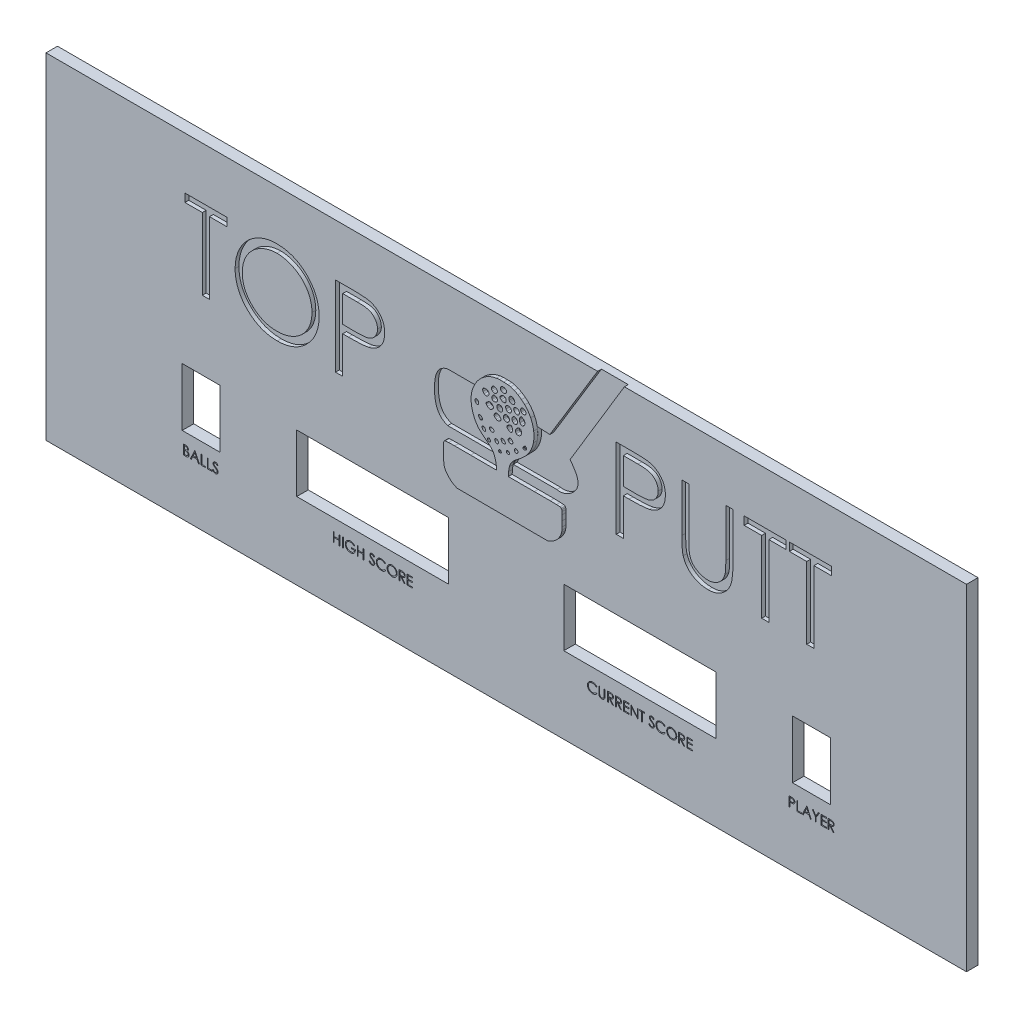
SolidWorks part; units mm, degrees
ref_plane "Front Plane" through (0, 0, 0) normal (0, 0, 1) x (1, 0, 0)
ref_plane "Top Plane" through (0, 0, 0) normal (0, 1, 0) x (1, 0, 0)
ref_plane "Right Plane" through (0, 0, 0) normal (1, 0, 0) x (0, 0, -1)
sketch "Sketch1" plane through (0, 0, 0) normal (0, 0, 1) x (1, 0, 0)
  line L1 (-152.4, 55.5625) -> (152.4, 55.5625)
  line L2 (-152.4, 55.5625) -> (-152.4, -55.5625)
  line L3 (-152.4, -55.5625) -> (152.4, -55.5625)
  line L4 (152.4, 55.5625) -> (152.4, -55.5625)
  line L5 (-152.4, 55.5625) -> (152.4, -55.5625) construction
  line L6 (-152.4, -55.5625) -> (152.4, 55.5625) construction
  point P0 (0, 0)
  dimension "D1" = 111.125
  dimension "D2" = 304.8
extrude "Boss-Extrude1" add sketch "Sketch1" along normal blind 3.81
sketch "Sketch3" plane through (0, 0, 3.81) normal (0, 0, 1) x (1, 0, 0)
  line L0 (-152.4, -30.1625) -> (152.4, -30.1625) construction
  line L1 (-152.4, 55.5625) -> (-152.4, -55.5625) construction
  line L2 (152.4, -55.5625) -> (152.4, 55.5625) construction
  line L3 (-152.4, -55.5625) -> (152.4, -55.5625) construction
  line L4 (0, 0) -> (0, -55.5625) construction
  line L5 (-94.775, -10.9805) -> (-107.3, -10.9805)
  line L6 (19.05, -30.1625) -> (69.375, -30.1625)
  line L7 (19.05, -30.1625) -> (19.05, -11.0725)
  line L8 (19.05, -11.0725) -> (69.375, -11.0725)
  line L9 (69.375, -30.1625) -> (69.375, -11.0725)
  line L10 (94.775, -30.1625) -> (107.3, -30.1625)
  line L11 (94.775, -30.1625) -> (94.775, -10.9805)
  line L12 (94.775, -10.9805) -> (107.3, -10.9805)
  line L13 (107.3, -30.1625) -> (107.3, -10.9805)
  line L14 (-107.3, -30.1625) -> (-107.3, -10.9805)
  line L15 (-94.775, -30.1625) -> (-107.3, -30.1625)
  line L16 (-94.775, -30.1625) -> (-94.775, -10.9805)
  line L17 (-19.05, -11.0725) -> (-69.375, -11.0725)
  line L18 (-69.375, -30.1625) -> (-69.375, -11.0725)
  line L19 (-19.05, -30.1625) -> (-69.375, -30.1625)
  line L20 (-19.05, -30.1625) -> (-19.05, -11.0725)
  dimension "D1" = 25.4
  dimension "D2" = 50.325
  dimension "D3" = 19.09
  dimension "D4" = 19.05
  dimension "D5" = 12.525
  dimension "D6" = 19.182
  dimension "D7" = 25.4
extrude "Cut-Extrude1" cut sketch "Sketch3" against normal blind 3.81
sketch "Sketch6" plane through (0, 0, 3.81) normal (0, 0, 1) x (1, 0, 0)
  line L0 (-107.3, -36.9875) -> (-94.775, -36.9875) construction
  line L1 (-57.6519, -37.2782) -> (-30.0792, -37.2782) construction
  line L2 (19.2892, -37.6268) -> (69.1358, -37.6268) construction
  line L3 (87.631, -37.6268) -> (114.444, -37.6268) construction
  line L4 (101.0375, -10.9805) -> (101.0375, -40.7176) construction
  line L5 (107.3, -10.9805) -> (94.775, -10.9805) construction
  line L6 (44.2125, -11.0725) -> (44.2125, -39.6653) construction
  line L7 (69.375, -11.0725) -> (19.05, -11.0725) construction
  text T0 "BALLS"
  text T1 "HIGH SCORE"
  text T2 "CURRENT SCORE"
  text T3 "PLAYER"
  point P10 (101.0375, -37.6268)
  point P19 (44.2125, -37.6268)
extrude "Cut-Extrude2" cut sketch "Sketch6" against normal blind 1.27
sketch "Sketch7" plane through (0, 0, 3.81) normal (0, 0, 1) x (1, 0, 0)
  line L20 (-1.9988, 12.5761) -> (-1.9988, 11.751)
  line L21 (-1.9988, 11.751) -> (-10.5132, 11.7768)
  line L22 (-15.9567, 0.4985) -> (-15.0481, 0.051)
  line L23 (-15.0481, 0.051) -> (0, 0)
  line L24 (0, 0) -> (15.0481, -0.051)
  line L25 (15.0481, -0.051) -> (16.2301, 0.5309)
  line L26 (10.5426, 11.862) -> (1.9524, 11.862)
  line L27 (1.9524, 11.862) -> (2.0672, 13.3498)
  line L31 (-3.3323, 25.2405) -> (-3.3323, 25.9331)
  line L32 (-5.0679, 26.8913) -> (-5.5861, 26.3948)
  line L33 (-5.5861, 26.3948) -> (-6.118, 27.1985)
  line L34 (-6.118, 27.1985) -> (-6.6498, 28.0022)
  line L35 (-6.6498, 28.0022) -> (-6.2293, 28.7329)
  line L36 (-3.7773, 36.3119) -> (-3.3529, 35.9132)
  line L37 (-3.3529, 35.9132) -> (-2.7235, 36.2908)
  arc A72 (-1.9988, 38.1147) -> (-4.7065, 37.2137) centre (-0.4765, 29.0205) ccw
  arc A73 (-4.7065, 37.2137) -> (-7.0856, 35.5114) centre (-0.0459, 28.1866) ccw
  arc A74 (-7.0856, 35.5114) -> (-8.9327, 33.1539) centre (0.3175, 27.8084) ccw
  arc A75 (-8.9327, 33.1539) -> (-10.0868, 30.3416) centre (0.8748, 27.4864) ccw
  arc A76 (-10.0868, 30.3416) -> (-10.3784, 27.9834) centre (-1.3361, 28.0623) ccw
  arc A77 (-10.3784, 27.9834) -> (-10.0835, 25.4534) centre (1.5107, 28.0871) ccw
  arc A78 (-10.0835, 25.4534) -> (-9.2506, 23.019) centre (1.7412, 28.1395) ccw
  arc A79 (-9.2506, 23.019) -> (-7.9518, 20.9428) centre (-0.2064, 27.2322) ccw
  arc A80 (-7.9518, 20.9428) -> (-7.5771, 20.537) centre (-4.5771, 23.6831) ccw
  arc A81 (-7.5771, 20.537) -> (-6.9573, 19.9681) centre (7.6292, 36.4839) ccw
  arc A82 (-6.9573, 19.9681) -> (-6.2356, 19.3549) centre (9.4942, 38.5956) ccw
  arc A83 (-6.2356, 19.3549) -> (-5.5071, 18.7837) centre (8.1333, 36.931) ccw
  arc A84 (-4.7279, 18.1675) -> (-5.5071, 18.7837) centre (-17.6705, 2.6013) ccw
  arc A85 (-4.0525, 17.5677) -> (-4.7279, 18.1675) centre (-13.5897, 7.5094) ccw
  arc A86 (-3.5128, 17.0173) -> (-4.0525, 17.5677) centre (-11.345, 9.8767) ccw
  arc A87 (-3.1609, 16.559) -> (-3.5128, 17.0173) centre (-6.0464, 14.7074) ccw
  arc A88 (-2.7104, 15.7011) -> (-3.1609, 16.559) centre (-7.8549, 13.5469) ccw
  arc A89 (-2.336, 14.6433) -> (-2.7104, 15.7011) centre (-11.9016, 11.8524) ccw
  arc A90 (-2.0823, 13.5482) -> (-2.336, 14.6433) centre (-11.9292, 11.8444) ccw
  arc A91 (-1.9988, 12.5761) -> (-2.0823, 13.5482) centre (-7.7002, 12.5761) ccw
  arc A92 (-10.5132, 11.7768) -> (-15.8316, 11.7851) centre (-15.9987, -1799.6541) ccw
  arc A93 (-15.8316, 11.7851) -> (-17.8341, 11.748) centre (-15.8365, -42.1127) ccw
  arc A94 (-17.8341, 11.748) -> (-18.9161, 11.666) centre (-17.3128, -2.308) ccw
  arc A95 (-18.9161, 11.666) -> (-19.2883, 11.4513) centre (-18.8545, 11.1292) ccw
  arc A96 (-19.2883, 11.4513) -> (-19.4186, 11.1338) centre (-18.73, 11.0367) ccw
  arc A97 (-19.4186, 11.1338) -> (-19.482, 10.4815) centre (-11.9086, 10.0751) ccw
  arc A98 (-19.482, 10.4815) -> (-19.5065, 9.4669) centre (-2.2361, 9.556) ccw
  arc A99 (-19.5065, 9.4669) -> (-19.4861, 7.7663) centre (104.1686, 10.1049) ccw
  arc A100 (-19.4861, 7.7663) -> (-19.4359, 5.7788) centre (136.9357, 10.7248) ccw
  arc A101 (-19.4359, 5.7788) -> (-19.3621, 4.8115) centre (-8.5243, 6.1239) ccw
  arc A102 (-19.3621, 4.8115) -> (-19.2237, 4.1547) centre (-15.5362, 5.2748) ccw
  arc A103 (-19.2237, 4.1547) -> (-18.9714, 3.5165) centre (-15.1935, 5.3789) ccw
  arc A104 (-18.9714, 3.5165) -> (-18.4339, 2.6452) centre (-14.1224, 5.9069) ccw
  arc A105 (-18.4339, 2.6452) -> (-17.6844, 1.7842) centre (-11.7934, 7.6688) ccw
  arc A106 (-17.6844, 1.7842) -> (-16.8249, 1.0345) centre (-11.8031, 7.659) ccw
  arc A107 (-16.8249, 1.0345) -> (-15.9567, 0.4985) centre (-13.594, 5.2965) ccw
  arc A108 (16.2301, 0.5309) -> (17.24, 1.1494) centre (13.3846, 6.3108) ccw
  arc A109 (17.24, 1.1494) -> (18.1193, 1.9421) centre (13.3896, 6.3041) ccw
  arc A110 (18.1193, 1.9421) -> (18.8359, 2.8798) centre (13.4202, 6.2759) ccw
  arc A111 (18.8359, 2.8798) -> (19.3634, 3.9283) centre (13.5385, 6.2018) ccw
  arc A112 (19.3634, 3.9283) -> (19.5889, 4.6371) centre (13.9478, 6.042) ccw
  arc A113 (19.5889, 4.6371) -> (19.714, 5.3482) centre (14.5796, 5.8846) ccw
  arc A114 (19.714, 5.3482) -> (19.7754, 6.3271) centre (7.9521, 6.577) ccw
  arc A115 (19.7754, 6.3271) -> (19.7983, 8.0917) centre (-88.8167, 8.6229) ccw
  arc A116 (19.7983, 8.0917) -> (19.7964, 9.866) centre (-128.5584, 8.8173) ccw
  arc A117 (19.7964, 9.866) -> (19.7533, 10.7144) centre (10.086, 9.7974) ccw
  arc A118 (19.7533, 10.7144) -> (19.6575, 11.21) centre (17.141, 10.4666) ccw
  arc A119 (19.6575, 11.21) -> (19.4731, 11.5207) centre (18.9527, 11.0018) ccw
  arc A120 (19.4731, 11.5207) -> (19.0432, 11.7268) centre (18.9668, 11.0158) ccw
  arc A121 (19.0432, 11.7268) -> (17.8903, 11.8106) centre (17.249, -4.9686) ccw
  arc A122 (17.8903, 11.8106) -> (15.8008, 11.8538) centre (15.6146, -47.7291) ccw
  arc A123 (15.8008, 11.8538) -> (10.5426, 11.862) centre (10.541, -1671.3002) ccw
  arc A124 (2.3284, 14.9123) -> (2.0672, 13.3498) centre (10.9883, 12.6616) ccw
  arc A125 (2.8492, 16.1436) -> (2.3284, 14.9123) centre (6.7809, 13.7551) ccw
  arc A126 (3.7446, 17.2566) -> (2.8492, 16.1436) centre (7.5014, 13.3174) ccw
  arc A127 (5.1762, 18.4675) -> (3.7446, 17.2566) centre (14.6019, 5.872) ccw
  arc A128 (5.1762, 18.4675) -> (6.4984, 19.5223) centre (-11.2086, 40.3625) ccw
  arc A129 (6.4984, 19.5223) -> (7.5394, 20.5023) centre (-2.5921, 30.2213) ccw
  arc A130 (7.5394, 20.5023) -> (8.3754, 21.4813) centre (-0.4957, 28.2102) ccw
  arc A131 (8.3754, 21.4813) -> (9.0734, 22.53) centre (0.2418, 27.6509) ccw
  arc A132 (9.0734, 22.53) -> (10.2566, 25.6998) centre (0.3306, 27.5994) ccw
  arc A133 (10.2566, 25.6998) -> (10.3539, 29.1346) centre (-0.285, 27.7172) ccw
  arc A134 (10.3539, 29.1346) -> (9.3609, 32.423) centre (-0.2778, 27.7181) ccw
  arc A135 (9.3609, 32.423) -> (7.3894, 35.1693) centre (0.3027, 28.0015) ccw
  arc A136 (7.3894, 35.1693) -> (6.3087, 36.1178) centre (-1.1236, 26.5589) ccw
  arc A137 (6.3087, 36.1178) -> (5.1303, 36.9244) centre (-0.9212, 26.8192) ccw
  arc A138 (5.1303, 36.9244) -> (3.9073, 37.5561) centre (-0.5041, 27.5156) ccw
  arc A139 (3.9073, 37.5561) -> (2.6935, 37.9815) centre (0.5388, 29.8894) ccw
  arc A140 (2.6935, 37.9815) -> (1.8123, 38.1326) centre (1.4189, 33.1946) ccw
  arc A141 (1.8123, 38.1326) -> (0.4204, 38.2078) centre (-0.3534, 10.9491) ccw
  arc A142 (0.4204, 38.2078) -> (-0.9951, 38.2105) centre (-0.3392, 11.4509) ccw
  arc A143 (-0.9951, 38.2105) -> (-1.9988, 38.1147) centre (-0.8202, 31.0736) ccw
  arc A144 (1.9506, 37.1033) -> (2.1398, 36.9355) centre (2.6538, 37.7054) ccw
  arc A145 (2.1398, 36.9355) -> (2.3755, 36.8163) centre (2.7492, 37.8482) ccw
  arc A146 (2.3755, 36.8163) -> (2.6619, 36.7456) centre (2.8528, 38.1344) ccw
  arc A147 (2.6619, 36.7456) -> (3.0026, 36.7223) centre (3.0026, 39.2238) ccw
  arc A148 (3.3292, 36.7021) -> (3.0026, 36.7223) centre (3.0026, 34.0711) ccw
  arc A149 (3.7121, 36.64) -> (3.3292, 36.7021) centre (2.6877, 31.5337) ccw
  arc A150 (4.0895, 36.5496) -> (3.7121, 36.64) centre (2.6875, 31.5325) ccw
  arc A151 (4.3988, 36.4422) -> (4.0895, 36.5496) centre (3.3743, 33.9902) ccw
  arc A152 (4.784, 36.2666) -> (4.3988, 36.4422) centre (1.8359, 30.3083) ccw
  arc A153 (4.9255, 36.1411) -> (4.784, 36.2666) centre (4.6248, 35.9448) ccw
  arc A154 (4.9476, 35.9915) -> (4.9255, 36.1411) centre (4.7741, 36.0423) ccw
  arc A155 (4.8495, 35.7517) -> (4.9476, 35.9915) centre (3.7411, 36.3449) ccw
  arc A156 (4.8495, 35.7517) -> (4.7549, 35.5183) centre (5.8958, 35.1917) ccw
  arc A157 (4.7549, 35.5183) -> (4.7439, 35.3239) centre (5.1795, 35.3968) ccw
  arc A158 (4.7439, 35.3239) -> (4.8182, 35.1186) centre (5.3397, 35.4236) ccw
  arc A159 (4.8182, 35.1186) -> (5.0017, 34.8411) centre (7.4222, 36.6413) ccw
  arc A160 (5.0017, 34.8411) -> (5.3678, 34.4786) centre (6.3777, 35.8645) ccw
  arc A161 (5.3678, 34.4786) -> (5.7824, 34.2984) centre (5.9784, 35.3166) ccw
  arc A162 (5.7824, 34.2984) -> (6.2007, 34.3213) centre (5.9458, 35.1468) ccw
  arc A163 (6.2007, 34.3213) -> (6.58, 34.5372) centre (5.903, 35.2853) ccw
  arc A164 (6.8097, 34.6751) -> (6.58, 34.5372) centre (7.0441, 34.0244) ccw
  arc A165 (6.9937, 34.6464) -> (6.8097, 34.6751) centre (6.8754, 34.4926) ccw
  arc A166 (7.2098, 34.4171) -> (6.9937, 34.6464) centre (6.3901, 33.8609) ccw
  arc A167 (7.7005, 33.6763) -> (7.2098, 34.4171) centre (-25.7222, 12.0742) ccw
  arc A168 (8.3128, 32.6868) -> (7.7005, 33.6763) centre (-17.2353, 17.5595) ccw
  arc A169 (8.5575, 32.1345) -> (8.3128, 32.6868) centre (6.0986, 31.3757) ccw
  arc A170 (8.5748, 31.7479) -> (8.5575, 32.1345) centre (7.8233, 31.9079) ccw
  arc A171 (8.4006, 31.4073) -> (8.5748, 31.7479) centre (7.8548, 31.9012) ccw
  arc A172 (8.4006, 31.4073) -> (8.1246, 30.848) centre (9.2455, 30.6427) ccw
  arc A173 (8.1246, 30.848) -> (8.1399, 30.1518) centre (9.8222, 30.537) ccw
  arc A174 (8.1399, 30.1518) -> (8.4431, 29.4431) centre (10.2485, 30.6346) ccw
  arc A175 (8.4431, 29.4431) -> (8.9852, 28.854) centre (10.5341, 30.8231) ccw
  arc A176 (9.2789, 28.5397) -> (8.9852, 28.854) centre (8.1107, 27.7422) ccw
  arc A177 (9.4149, 28.1908) -> (9.2789, 28.5397) centre (8.5931, 28.0716) ccw
  arc A178 (9.3647, 27.8926) -> (9.4149, 28.1908) centre (8.9255, 28.1198) ccw
  arc A179 (9.1523, 27.7025) -> (9.3647, 27.8926) centre (9.0087, 28.0768) ccw
  arc A180 (9.0102, 27.6969) -> (9.1523, 27.7025) centre (9.073, 27.9091) ccw
  arc A181 (8.8404, 27.7767) -> (9.0102, 27.6969) centre (9.1867, 28.2932) ccw
  arc A182 (8.6565, 27.9332) -> (8.8404, 27.7767) centre (9.4295, 28.6552) ccw
  arc A183 (8.4727, 28.1582) -> (8.6565, 27.9332) centre (10.2596, 29.4306) ccw
  arc A184 (8.4727, 28.1582) -> (8.1185, 28.5075) centre (7.2994, 27.3227) ccw
  arc A185 (8.1185, 28.5075) -> (7.7735, 28.5635) centre (7.8871, 28.1729) ccw
  arc A186 (7.7735, 28.5635) -> (7.4459, 28.3259) centre (7.9408, 27.9883) ccw
  arc A187 (7.4459, 28.3259) -> (7.1468, 27.7726) centre (9.9735, 26.6017) ccw
  arc A188 (7.1468, 27.7726) -> (7.0351, 27.4291) centre (9.2757, 26.8908) ccw
  arc A189 (7.0351, 27.4291) -> (7.0097, 27.1396) centre (7.9925, 27.199) ccw
  arc A190 (7.0097, 27.1396) -> (7.0684, 26.8133) centre (8.4186, 27.2248) ccw
  arc A191 (7.0684, 26.8133) -> (7.234, 26.3303) centre (14.1531, 28.9727) ccw
  arc A192 (7.4215, 25.6708) -> (7.234, 26.3303) centre (3.5848, 24.9367) ccw
  arc A193 (7.3678, 25.2424) -> (7.4215, 25.6708) centre (6.7346, 25.5394) ccw
  arc A194 (7.0889, 24.995) -> (7.3678, 25.2424) centre (6.9411, 25.4425) ccw
  arc A195 (6.5685, 24.9113) -> (7.0889, 24.995) centre (6.5685, 26.5706) ccw
  arc A196 (6.5685, 24.9113) -> (6.2779, 24.8678) centre (6.5685, 23.9183) ccw
  arc A197 (6.2779, 24.8678) -> (6.0439, 24.7415) centre (6.4757, 24.2214) ccw
  arc A198 (6.0439, 24.7415) -> (5.8175, 24.4947) centre (6.8354, 23.7882) ccw
  arc A199 (5.8175, 24.4947) -> (5.536, 24.054) centre (11.4216, 20.6049) ccw
  arc A200 (5.3305, 23.7256) -> (5.536, 24.054) centre (-0.2045, 27.4182) ccw
  arc A201 (5.1284, 23.4486) -> (5.3305, 23.7256) centre (1.9261, 25.9968) ccw
  arc A202 (4.949, 23.2386) -> (5.1284, 23.4486) centre (2.0335, 25.9113) ccw
  arc A203 (4.8539, 23.1968) -> (4.949, 23.2386) centre (4.8539, 23.3258) ccw
  arc A204 (4.7581, 23.2351) -> (4.8539, 23.1968) centre (4.8539, 23.3357) ccw
  arc A206 (4.3819, 23.6581) -> (4.5815, 23.4164) centre (7.2527, 25.8264) ccw
  arc A207 (4.1793, 23.9445) -> (4.3819, 23.6581) centre (8.8785, 27.0543) ccw
  arc A208 (4.1793, 23.9445) -> (3.9693, 24.2386) centre (-0.0706, 21.132) ccw
  arc A209 (3.9693, 24.2386) -> (3.7474, 24.5042) centre (0.574, 21.6278) ccw
  arc A210 (3.7474, 24.5042) -> (3.5429, 24.7126) centre (1.0186, 22.0308) ccw
  arc A211 (3.5429, 24.7126) -> (3.404, 24.7998) centre (3.2519, 24.4034) ccw
  arc A212 (3.404, 24.7998) -> (3.1041, 24.7728) centre (3.2816, 24.4809) ccw
  arc A213 (3.1041, 24.7728) -> (2.6747, 24.4492) centre (4.5104, 22.4598) ccw
  arc A214 (2.6747, 24.4492) -> (2.3057, 24.0329) centre (4.5591, 22.407) ccw
  arc A215 (2.3057, 24.0329) -> (2.1922, 23.6817) centre (2.7924, 23.6817) ccw
  arc A216 (2.1731, 23.5693) -> (2.1922, 23.6817) centre (1.8522, 23.6817) ccw
  arc A217 (2.118, 23.4738) -> (2.1731, 23.5693) centre (1.8918, 23.6678) ccw
  arc A218 (2.036, 23.4099) -> (2.118, 23.4738) centre (1.9197, 23.6439) ccw
  arc A219 (1.9396, 23.3873) -> (2.036, 23.4099) centre (1.9396, 23.6037) ccw
  arc A220 (1.6068, 23.5088) -> (1.9396, 23.3873) centre (1.9396, 23.9039) ccw
  arc A221 (1.2363, 23.899) -> (1.6068, 23.5088) centre (3.1678, 25.3622) ccw
  arc A222 (0.9035, 24.4434) -> (1.2363, 23.899) centre (3.7917, 25.8348) ccw
  arc A223 (0.6784, 25.0522) -> (0.9035, 24.4434) centre (3.9938, 25.9321) ccw
  arc A224 (0.6784, 25.0522) -> (0.5525, 25.444) centre (-3.1784, 24.0287) ccw
  arc A225 (0.5525, 25.444) -> (0.4114, 25.7058) centre (-0.5061, 25.0424) ccw
  arc A226 (0.4114, 25.7058) -> (0.2369, 25.8738) centre (-0.1422, 25.3055) ccw
  arc A227 (0.2369, 25.8738) -> (0.0123, 25.9733) centre (-0.1631, 25.2742) ccw
  arc A228 (0.0123, 25.9733) -> (-0.4132, 25.9958) centre (-0.2578, 24.897) ccw
  arc A229 (-0.4132, 25.9958) -> (-0.8377, 25.8598) centre (-0.2282, 24.6876) ccw
  arc A230 (-0.8377, 25.8598) -> (-1.1913, 25.5912) centre (-0.2331, 24.697) ccw
  arc A231 (-1.1913, 25.5912) -> (-1.413, 25.2322) centre (-0.405, 24.8575) ccw
  arc A232 (-1.413, 25.2322) -> (-1.5077, 24.8341) centre (0.1568, 24.6486) ccw
  arc A233 (-1.5077, 24.8341) -> (-1.4439, 24.5581) centre (-1.0835, 24.7868) ccw
  arc A234 (-1.4439, 24.5581) -> (-1.2258, 24.3941) centre (-1.1172, 24.7655) ccw
  arc A235 (-1.2258, 24.3941) -> (-0.8467, 24.3398) centre (-0.8467, 25.6906) ccw
  arc A236 (-0.4429, 24.292) -> (-0.8467, 24.3398) centre (-0.8467, 22.6099) ccw
  arc A237 (-0.21, 24.1414) -> (-0.4429, 24.292) centre (-0.5405, 23.8856) ccw
  arc A238 (-0.1218, 23.8775) -> (-0.21, 24.1414) centre (-0.5435, 23.8833) ccw
  arc A239 (-0.1748, 23.4717) -> (-0.1218, 23.8775) centre (-1.8884, 23.9018) ccw
  arc A240 (-0.5175, 23.0837) -> (-0.1748, 23.4717) centre (-0.721, 23.6088) ccw
  arc A241 (-1.0788, 23.0959) -> (-0.5175, 23.0837) centre (-0.7834, 23.7699) ccw
  arc A242 (-1.6098, 23.5388) -> (-1.0788, 23.0959) centre (-0.5801, 24.2336) ccw
  arc A243 (-1.8083, 24.1878) -> (-1.6098, 23.5388) centre (-0.648, 24.1878) ccw
  arc A244 (-1.8083, 24.1878) -> (-1.8584, 24.3489) centre (-2.0926, 24.1878) ccw
  arc A245 (-1.8584, 24.3489) -> (-2.0189, 24.537) centre (-2.8411, 23.673) ccw
  arc A246 (-2.0189, 24.537) -> (-2.2609, 24.7304) centre (-3.2553, 23.2377) ccw
  arc A247 (-2.2609, 24.7304) -> (-2.5667, 24.9094) centre (-3.9564, 22.1853) ccw
  arc A248 (-4.1862, 23.9933) -> (-3.8152, 24.5198) centre (-9.1823, 27.908) ccw
  arc A249 (-4.4423, 23.8477) -> (-4.1862, 23.9933) centre (-4.4917, 24.2326) ccw
  arc A250 (-4.6869, 23.9418) -> (-4.4423, 23.8477) centre (-4.4774, 24.1215) ccw
  arc A251 (-4.9962, 24.3685) -> (-4.6869, 23.9418) centre (-2.2415, 26.0399) ccw
  arc A252 (-5.2264, 24.8852) -> (-4.9962, 24.3685) centre (-3.076, 25.5335) ccw
  arc A253 (-5.1616, 25.2168) -> (-5.2264, 24.8852) centre (-4.8802, 24.9896) ccw
  arc A254 (-4.8345, 25.3845) -> (-5.1616, 25.2168) centre (-4.8091, 24.9323) ccw
  arc A255 (-4.1966, 25.359) -> (-4.8345, 25.3845) centre (-4.6481, 22.0647) ccw
  arc A256 (-3.3323, 25.9331) -> (-3.4134, 26.4403) centre (-4.9588, 25.9331) ccw
  arc A257 (-3.4134, 26.4403) -> (-3.6499, 26.921) centre (-5.2351, 25.8425) ccw
  arc A258 (-3.6499, 26.921) -> (-3.9769, 27.2694) centre (-4.9195, 26.0572) ccw
  arc A259 (-3.9769, 27.2694) -> (-4.322, 27.3878) centre (-4.322, 26.8255) ccw
  arc A260 (-4.322, 27.3878) -> (-4.4418, 27.3577) centre (-4.322, 27.1343) ccw
  arc A261 (-4.4418, 27.3577) -> (-4.6351, 27.2419) centre (-3.3239, 25.2721) ccw
  arc A262 (-4.6351, 27.2419) -> (-4.8528, 27.0814) centre (-3.0752, 24.8984) ccw
  arc A263 (-4.8528, 27.0814) -> (-5.0679, 26.8913) centre (-2.6027, 24.3182) ccw
  arc A264 (-6.2293, 28.7329) -> (-5.9152, 29.3228) centre (-15.0097, 33.7862) ccw
  arc A265 (-5.9152, 29.3228) -> (-5.8361, 29.646) centre (-6.6116, 29.6645) ccw
  arc A266 (-5.8361, 29.646) -> (-5.9156, 29.9143) centre (-6.2918, 29.6569) ccw
  arc A267 (-5.9156, 29.9143) -> (-6.193, 30.2485) centre (-7.8529, 28.5886) ccw
  arc A268 (-6.193, 30.2485) -> (-6.4341, 30.4622) centre (-8.0881, 28.3535) ccw
  arc A269 (-6.4341, 30.4622) -> (-6.6038, 30.5305) centre (-6.6368, 30.2039) ccw
  arc A270 (-6.6038, 30.5305) -> (-6.7958, 30.5022) centre (-6.6436, 30.1362) ccw
  arc A271 (-6.7958, 30.5022) -> (-7.1361, 30.3438) centre (-5.0626, 26.3341) ccw
  arc A272 (-7.6259, 30.1023) -> (-7.1361, 30.3438) centre (-13.6756, 42.9899) ccw
  arc A273 (-7.7962, 30.0866) -> (-7.6259, 30.1023) centre (-7.7326, 30.3297) ccw
  arc A274 (-7.8844, 30.1887) -> (-7.7962, 30.0866) centre (-7.766, 30.2019) ccw
  arc A275 (-7.9043, 30.5446) -> (-7.8844, 30.1887) centre (-4.7062, 30.5446) ccw
  arc A276 (-7.9043, 30.5446) -> (-7.9253, 30.7532) centre (-8.9494, 30.5446) ccw
  arc A277 (-7.9253, 30.7532) -> (-7.9883, 30.9745) centre (-9.4094, 30.451) ccw
  arc A278 (-7.9883, 30.9745) -> (-8.0805, 31.1753) centre (-9.3205, 30.4837) ccw
  arc A279 (-8.0805, 31.1753) -> (-8.1901, 31.3203) centre (-8.6559, 30.8544) ccw
  arc A280 (-8.2994, 31.4536) -> (-8.1901, 31.3203) centre (-7.5702, 31.9401) ccw
  arc A281 (-8.3919, 31.6179) -> (-8.2994, 31.4536) centre (-7.2631, 32.145) ccw
  arc A282 (-8.4552, 31.7865) -> (-8.3919, 31.6179) centre (-7.3411, 32.1085) ccw
  arc A283 (-8.4758, 31.9322) -> (-8.4552, 31.7865) centre (-7.9512, 31.9322) ccw
  arc A284 (-8.398, 32.2511) -> (-8.4758, 31.9322) centre (-7.7831, 31.9322) ccw
  arc A285 (-7.9746, 33.0319) -> (-8.398, 32.2511) centre (12.8903, 21.2109) ccw
  arc A286 (-7.4571, 33.8916) -> (-7.9746, 33.0319) centre (8.5525, 23.6685) ccw
  arc A287 (-6.9069, 34.7014) -> (-7.4571, 33.8916) centre (7.0492, 24.6285) ccw
  arc A288 (-6.7433, 34.9178) -> (-6.9069, 34.7014) centre (-1.9405, 31.1168) ccw
  arc A289 (-6.6874, 34.9248) -> (-6.7433, 34.9178) centre (-6.7118, 34.8928) ccw
  arc A290 (-6.6544, 34.8588) -> (-6.6874, 34.9248) centre (-6.738, 34.8583) ccw
  arc A291 (-6.6565, 34.5109) -> (-6.6544, 34.8588) centre (-21.7871, 34.7747) ccw
  arc A292 (-6.6565, 34.5109) -> (-6.5581, 34.1042) centre (-5.8267, 34.4964) ccw
  arc A293 (-6.5581, 34.1042) -> (-6.2854, 33.9033) centre (-6.2103, 34.2907) ccw
  arc A294 (-6.2854, 33.9033) -> (-5.8645, 33.9525) centre (-6.1523, 34.59) ccw
  arc A295 (-5.8645, 33.9525) -> (-5.3587, 34.2593) centre (-6.8707, 36.1816) ccw
  arc A296 (-5.3587, 34.2593) -> (-4.9822, 34.6674) centre (-6.4412, 35.6355) ccw
  arc A297 (-4.9822, 34.6674) -> (-4.8828, 35.0746) centre (-5.4965, 35.0087) ccw
  arc A298 (-4.8828, 35.0746) -> (-5.0705, 35.3878) centre (-5.3157, 35.0281) ccw
  arc A299 (-5.0705, 35.3878) -> (-5.4968, 35.5464) centre (-5.6045, 34.6043) ccw
  arc A300 (-5.8624, 35.5925) -> (-5.4968, 35.5464) centre (-3.702, 51.2441) ccw
  arc A301 (-5.9198, 35.6372) -> (-5.8624, 35.5925) centre (-5.8524, 35.6645) ccw
  arc A302 (-5.9022, 35.7003) -> (-5.9198, 35.6372) centre (-5.8701, 35.6573) ccw
  arc A303 (-5.637, 35.8925) -> (-5.9022, 35.7003) centre (0.2512, 27.4859) ccw
  arc A304 (-5.445, 36.0203) -> (-5.637, 35.8925) centre (-2.8263, 31.8797) ccw
  arc A305 (-5.1996, 36.1714) -> (-5.445, 36.0203) centre (0.8644, 26.0438) ccw
  arc A306 (-4.9435, 36.3205) -> (-5.1996, 36.1714) centre (1.076, 25.6905) ccw
  arc A307 (-4.7168, 36.4434) -> (-4.9435, 36.3205) centre (-1.4784, 30.2014) ccw
  arc A308 (-4.4091, 36.582) -> (-4.7168, 36.4434) centre (-3.3163, 33.744) ccw
  arc A309 (-4.2162, 36.6041) -> (-4.4091, 36.582) centre (-4.2699, 36.2205) ccw
  arc A310 (-4.0365, 36.5299) -> (-4.2162, 36.6041) centre (-4.2702, 36.2188) ccw
  arc A311 (-3.7773, 36.3119) -> (-4.0365, 36.5299) centre (-5.8857, 34.0677) ccw
  arc A312 (-2.7235, 36.2908) -> (-2.4867, 36.4535) centre (-3.9204, 38.2859) ccw
  arc A313 (-2.4867, 36.4535) -> (-2.2959, 36.6302) centre (-3.4524, 37.6878) ccw
  arc A314 (-2.2959, 36.6302) -> (-2.1714, 36.7954) centre (-3.1027, 37.368) ccw
  arc A315 (-2.1714, 36.7954) -> (-2.1517, 36.916) centre (-2.3082, 36.8796) ccw
  arc A316 (-2.079, 37.1815) -> (-2.1517, 36.916) centre (-1.8701, 36.9816) ccw
  arc A317 (-1.7793, 37.359) -> (-2.079, 37.1815) centre (-1.6118, 36.7343) ccw
  arc A318 (-1.16, 37.455) -> (-1.7793, 37.359) centre (-1.0283, 34.5595) ccw
  arc A319 (-0.0443, 37.4814) -> (-1.16, 37.455) centre (0.0003, 11.9494) ccw
  arc A320 (0.8891, 37.4696) -> (-0.0443, 37.4814) centre (0.0125, 4.9719) ccw
  arc A321 (1.3861, 37.4161) -> (0.8891, 37.4696) centre (0.8049, 34.3495) ccw
  arc A322 (1.7033, 37.3032) -> (1.3861, 37.4161) centre (1.1828, 36.3433) ccw
  arc A323 (1.9506, 37.1033) -> (1.7033, 37.3032) centre (1.2866, 36.5347) ccw
  arc A324 (-7.9382, 28.3453) -> (-8.1329, 28.6832) centre (-8.6641, 28.152) ccw
  arc A325 (-7.8994, 27.8963) -> (-7.9382, 28.3453) centre (-9.195, 28.0106) ccw
  arc A326 (-8.0138, 27.5248) -> (-7.8994, 27.8963) centre (-8.8253, 27.978) ccw
  arc A327 (-8.2472, 27.3878) -> (-8.0138, 27.5248) centre (-8.2472, 27.6551) ccw
  arc A328 (-8.5616, 27.4519) -> (-8.2472, 27.3878) centre (-8.2472, 28.1909) ccw
  arc A329 (-8.8197, 27.6334) -> (-8.5616, 27.4519) centre (-8.2662, 28.1463) ccw
  arc A330 (-8.9885, 27.9118) -> (-8.8197, 27.6334) centre (-8.2252, 28.1842) ccw
  arc A331 (-9.0473, 28.2514) -> (-8.9885, 27.9118) centre (-8.0371, 28.2514) ccw
  arc A332 (-8.9728, 28.6569) -> (-9.0473, 28.2514) centre (-7.9068, 28.2514) ccw
  arc A333 (-8.7599, 28.887) -> (-8.9728, 28.6569) centre (-8.5808, 28.5078) ccw
  arc A334 (-8.4587, 28.8969) -> (-8.7599, 28.887) centre (-8.5979, 28.5439) ccw
  arc A335 (-8.1329, 28.6832) -> (-8.4587, 28.8969) centre (-8.81, 28.0061) ccw
  arc A336 (-6.6162, 24.1598) -> (-6.7204, 24.4214) centre (-9.3712, 23.2136) ccw
  arc A337 (-6.5951, 23.9936) -> (-6.6162, 24.1598) centre (-7.007, 24.0256) ccw
  arc A338 (-6.6452, 23.8695) -> (-6.5951, 23.9936) centre (-6.8164, 24.0108) ccw
  arc A339 (-6.7721, 23.7576) -> (-6.6452, 23.8695) centre (-7.0591, 24.211) ccw
  arc A340 (-6.8869, 23.6908) -> (-6.7721, 23.7576) centre (-7.7337, 25.2773) ccw
  arc A341 (-7.0043, 23.6339) -> (-6.8869, 23.6908) centre (-7.6766, 25.1703) ccw
  arc A342 (-7.1089, 23.5929) -> (-7.0043, 23.6339) centre (-7.5816, 24.9533) ccw
  arc A343 (-7.1763, 23.5807) -> (-7.1089, 23.5929) centre (-7.1813, 23.8013) ccw
  arc A344 (-7.3898, 23.6584) -> (-7.1763, 23.5807) centre (-7.1834, 23.8935) ccw
  arc A345 (-7.6393, 23.9269) -> (-7.3898, 23.6584) centre (-6.1973, 25.0167) ccw
  arc A346 (-7.8396, 24.2569) -> (-7.6393, 23.9269) centre (-6.1238, 25.0723) ccw
  arc A347 (-7.9043, 24.5439) -> (-7.8396, 24.2569) centre (-7.2357, 24.5439) ccw
  arc A348 (-7.7589, 24.836) -> (-7.9043, 24.5439) centre (-7.5383, 24.5439) ccw
  arc A349 (-7.417, 24.9312) -> (-7.7589, 24.836) centre (-7.4669, 24.4493) ccw
  arc A350 (-7.0042, 24.7713) -> (-7.417, 24.9312) centre (-7.5036, 24.0947) ccw
  arc A351 (-6.7204, 24.4214) -> (-7.0042, 24.7713) centre (-7.5371, 24.0493) ccw
  arc A352 (8.0131, 22.841) -> (7.9072, 23.1015) centre (7.5486, 22.8039) ccw
  arc A353 (7.9461, 22.574) -> (8.0131, 22.841) centre (7.584, 22.8068) ccw
  arc A354 (7.7016, 22.3415) -> (7.9461, 22.574) centre (7.3472, 22.959) ccw
  arc A355 (7.3178, 22.1844) -> (7.7016, 22.3415) centre (6.9211, 23.7014) ccw
  arc A356 (7.0078, 22.1926) -> (7.3178, 22.1844) centre (7.1769, 22.7232) ccw
  arc A357 (6.8297, 22.3712) -> (7.0078, 22.1926) centre (7.091, 22.4536) ccw
  arc A358 (6.8434, 22.6774) -> (6.8297, 22.3712) centre (7.2559, 22.5056) ccw
  arc A359 (7.0564, 23.0134) -> (6.8434, 22.6774) centre (7.9254, 22.2269) ccw
  arc A360 (7.3307, 23.2844) -> (7.0564, 23.0134) centre (9.6123, 20.7003) ccw
  arc A361 (7.5175, 23.3663) -> (7.3307, 23.2844) centre (7.552, 23.0337) ccw
  arc A362 (7.6915, 23.3146) -> (7.5175, 23.3663) centre (7.542, 23.13) ccw
  arc A363 (7.9072, 23.1015) -> (7.6915, 23.3146) centre (6.7232, 22.1189) ccw
  arc A364 (-2.7813, 22.5799) -> (-2.9589, 22.9202) centre (-3.6618, 22.3368) ccw
  arc A365 (-2.8081, 22.2627) -> (-2.7813, 22.5799) centre (-3.2242, 22.4576) ccw
  arc A366 (-3.0346, 22.0393) -> (-2.8081, 22.2627) centre (-3.2235, 22.4573) ccw
  arc A367 (-3.4094, 21.9585) -> (-3.0346, 22.0393) centre (-3.4094, 22.8687) ccw
  arc A368 (-3.8114, 22.0321) -> (-3.4094, 21.9585) centre (-3.4094, 23.0939) ccw
  arc A369 (-4.1145, 22.2418) -> (-3.8114, 22.0321) centre (-3.5406, 22.7475) ccw
  arc A370 (-4.2596, 22.5457) -> (-4.1145, 22.2418) centre (-3.6524, 22.6489) ccw
  arc A371 (-4.2259, 22.8851) -> (-4.2596, 22.5457) centre (-3.6232, 22.6539) ccw
  arc A372 (-4.0223, 23.1017) -> (-4.2259, 22.8851) centre (-3.8591, 22.7444) ccw
  arc A373 (-3.653, 23.1875) -> (-4.0223, 23.1017) centre (-3.6267, 22.2358) ccw
  arc A374 (-3.251, 23.124) -> (-3.653, 23.1875) centre (-3.6223, 22.0763) ccw
  arc A375 (-2.9589, 22.9202) -> (-3.251, 23.124) centre (-3.475, 22.4918) ccw
  arc A376 (3.4136, 22.5967) -> (3.25, 22.8046) centre (1.8251, 21.5151) ccw
  arc A377 (3.4861, 22.4274) -> (3.4136, 22.5967) centre (3.0177, 22.3271) ccw
  arc A378 (3.4811, 22.2668) -> (3.4861, 22.4274) centre (3.1583, 22.3572) ccw
  arc A379 (3.403, 22.0903) -> (3.4811, 22.2668) centre (2.8303, 22.4492) ccw
  arc A380 (3.125, 21.8262) -> (3.403, 22.0903) centre (2.7496, 22.4997) ccw
  arc A381 (2.7359, 21.7074) -> (3.125, 21.8262) centre (2.6546, 22.6703) ccw
  arc A382 (2.3449, 21.7611) -> (2.7359, 21.7074) centre (2.66, 22.6059) ccw
  arc A383 (2.06, 21.9769) -> (2.3449, 21.7611) centre (2.5624, 22.3442) ccw
  arc A384 (1.8738, 22.2686) -> (2.06, 21.9769) centre (4.2678, 23.5913) ccw
  arc A385 (1.8289, 22.4647) -> (1.8738, 22.2686) centre (2.1927, 22.4447) ccw
  arc A386 (1.896, 22.6495) -> (1.8289, 22.4647) centre (2.1684, 22.4461) ccw
  arc A387 (2.1105, 22.8974) -> (1.896, 22.6495) centre (3.7223, 21.2857) ccw
  arc A388 (2.4017, 23.1187) -> (2.1105, 22.8974) centre (3.0664, 21.9416) ccw
  arc A389 (2.6718, 23.178) -> (2.4017, 23.1187) centre (2.6335, 22.7082) ccw
  arc A390 (2.9455, 23.0771) -> (2.6718, 23.178) centre (2.6276, 22.6364) ccw
  arc A391 (3.25, 22.8046) -> (2.9455, 23.0771) centre (1.8076, 21.4992) ccw
  arc A392 (-5.7592, 21.8957) -> (-5.8469, 22.0157) centre (-6.1891, 21.6735) ccw
  arc A393 (-5.6855, 21.7216) -> (-5.7592, 21.8957) centre (-6.8592, 21.3271) ccw
  arc A394 (-5.6352, 21.5253) -> (-5.6855, 21.7216) centre (-6.9933, 21.282) ccw
  arc A395 (-5.6183, 21.3357) -> (-5.6352, 21.5253) centre (-6.6935, 21.3357) ccw
  arc A396 (-5.6374, 21.1123) -> (-5.6183, 21.3357) centre (-6.9323, 21.3357) ccw
  arc A397 (-5.7027, 20.9899) -> (-5.6374, 21.1123) centre (-5.8554, 21.1499) ccw
  arc A398 (-5.8238, 20.9368) -> (-5.7027, 20.9899) centre (-5.8364, 21.13) ccw
  arc A399 (-6.0275, 20.9452) -> (-5.8238, 20.9368) centre (-5.8863, 21.894) ccw
  arc A400 (-6.3597, 21.0667) -> (-6.0275, 20.9452) centre (-5.8985, 21.8124) ccw
  arc A401 (-6.6131, 21.3089) -> (-6.3597, 21.0667) centre (-5.9146, 21.7863) ccw
  arc A402 (-6.7358, 21.6189) -> (-6.6131, 21.3089) centre (-5.9901, 21.7347) ccw
  arc A403 (-6.7024, 21.9326) -> (-6.7358, 21.6189) centre (-6.1299, 21.713) ccw
  arc A404 (-6.5568, 22.1405) -> (-6.7024, 21.9326) centre (-6.2133, 21.745) ccw
  arc A405 (-6.3426, 22.2325) -> (-6.5568, 22.1405) centre (-6.3056, 21.8512) ccw
  arc A406 (-6.0917, 22.1885) -> (-6.3426, 22.2325) centre (-6.2965, 21.758) ccw
  arc A407 (-5.8469, 22.0157) -> (-6.0917, 22.1885) centre (-6.4708, 21.3918) ccw
  arc A408 (0.9604, 21.0226) -> (0.7755, 21.3954) centre (-0.6831, 20.4397) ccw
  arc A409 (0.9483, 20.7526) -> (0.9604, 21.0226) centre (0.6219, 20.9025) ccw
  arc A410 (0.7553, 20.585) -> (0.9483, 20.7526) centre (0.6665, 20.882) ccw
  arc A411 (0.3779, 20.5298) -> (0.7553, 20.585) centre (0.3779, 21.8475) ccw
  arc A412 (0.032, 20.6252) -> (0.3779, 20.5298) centre (0.3779, 21.2043) ccw
  arc A413 (-0.2626, 20.8935) -> (0.032, 20.6252) centre (0.5458, 21.4854) ccw
  arc A414 (-0.4249, 21.2497) -> (-0.2626, 20.8935) centre (0.5147, 21.4626) ccw
  arc A415 (-0.4002, 21.5924) -> (-0.4249, 21.2497) centre (0.1522, 21.3805) ccw
  arc A416 (-0.1993, 21.8051) -> (-0.4002, 21.5924) centre (-0.0414, 21.4547) ccw
  arc A417 (0.1234, 21.8469) -> (-0.1993, 21.8051) centre (0.0308, 21.2944) ccw
  arc A418 (0.485, 21.6973) -> (0.1234, 21.8469) centre (-0.0208, 20.9865) ccw
  arc A419 (0.7755, 21.3954) -> (0.485, 21.6973) centre (-0.1712, 20.7751) ccw
  arc A420 (5.1043, 20.7177) -> (5.0296, 20.8397) centre (4.6451, 20.5205) ccw
  arc A421 (5.1497, 20.5682) -> (5.1043, 20.7177) centre (4.4539, 20.4384) ccw
  arc A422 (5.1608, 20.4152) -> (5.1497, 20.5682) centre (4.4767, 20.4427) ccw
  arc A423 (5.1335, 20.2829) -> (5.1608, 20.4152) centre (4.7452, 20.4319) ccw
  arc A424 (4.8129, 19.9256) -> (5.1335, 20.2829) centre (4.5053, 20.524) ccw
  arc A425 (4.3564, 19.8971) -> (4.8129, 19.9256) centre (4.5522, 20.4328) ccw
  arc A426 (4.0199, 20.2144) -> (4.3564, 19.8971) centre (4.5576, 20.4476) ccw
  arc A427 (3.9952, 20.699) -> (4.0199, 20.2144) centre (4.6547, 20.4897) ccw
  arc A428 (4.1667, 20.9609) -> (3.9952, 20.699) centre (4.5494, 20.5231) ccw
  arc A429 (4.4447, 21.0873) -> (4.1667, 20.9609) centre (4.5162, 20.5611) ccw
  arc A430 (4.7599, 21.0431) -> (4.4447, 21.0873) centre (4.5238, 20.5056) ccw
  arc A431 (5.0296, 20.8397) -> (4.7599, 21.0431) centre (4.4644, 20.3706) ccw
  arc A432 (-1.3206, 19.9944) -> (-1.4347, 20.3531) centre (-2.3442, 19.8664) ccw
  arc A433 (-1.3701, 19.6729) -> (-1.3206, 19.9944) centre (-1.9103, 19.9206) ccw
  arc A434 (-1.5678, 19.4698) -> (-1.3701, 19.6729) centre (-1.7542, 19.849) ccw
  arc A435 (-1.8607, 19.4243) -> (-1.5678, 19.4698) centre (-1.7871, 19.9159) ccw
  arc A436 (-2.1798, 19.5452) -> (-1.8607, 19.4243) centre (-1.7413, 20.2212) ccw
  arc A437 (-2.4252, 19.7885) -> (-2.1798, 19.5452) centre (-1.7194, 20.255) ccw
  arc A438 (-2.5448, 20.0987) -> (-2.4252, 19.7885) centre (-1.7786, 20.2159) ccw
  arc A439 (-2.5114, 20.4086) -> (-2.5448, 20.0987) centre (-1.9433, 20.1907) ccw
  arc A440 (-2.3157, 20.6354) -> (-2.5114, 20.4086) centre (-2.0987, 20.2503) ccw
  arc A441 (-2.0015, 20.7092) -> (-2.3157, 20.6354) centre (-2.0313, 20.1307) ccw
  arc A442 (-1.6699, 20.6047) -> (-2.0015, 20.7092) centre (-2.0372, 20.0174) ccw
  arc A443 (-1.4347, 20.3531) -> (-1.6699, 20.6047) centre (-2.0248, 20.0373) ccw
  arc A444 (-3.9647, 19.2154) -> (-4.0963, 19.4845) centre (-4.5855, 19.0785) ccw
  arc A445 (-3.9775, 18.9259) -> (-3.9647, 19.2154) centre (-4.5126, 19.0946) ccw
  arc A446 (-4.1278, 18.708) -> (-3.9775, 18.9259) centre (-4.4069, 19.0612) ccw
  arc A447 (-4.3674, 18.6248) -> (-4.1278, 18.708) centre (-4.3674, 19.0113) ccw
  arc A448 (-4.6383, 18.7203) -> (-4.3674, 18.6248) centre (-4.3674, 19.0565) ccw
  arc A449 (-4.8458, 18.9826) -> (-4.6383, 18.7203) centre (-4.164, 19.3089) ccw
  arc A450 (-4.9148, 19.2999) -> (-4.8458, 18.9826) centre (-4.2097, 19.287) ccw
  arc A451 (-4.8093, 19.5481) -> (-4.9148, 19.2999) centre (-4.5545, 19.2933) ccw
  arc A452 (-4.6095, 19.712) -> (-4.8093, 19.5481) centre (-3.8771, 18.6159) ccw
  arc A453 (-4.4502, 19.7527) -> (-4.6095, 19.712) centre (-4.4722, 19.5065) ccw
  arc A454 (-4.2927, 19.6856) -> (-4.4502, 19.7527) centre (-4.4749, 19.4764) ccw
  arc A455 (-4.0963, 19.4845) -> (-4.2927, 19.6856) centre (-5.438, 18.371) ccw
  arc A456 (2.3579, 18.4532) -> (2.3483, 18.6724) centre (1.2294, 18.5135) ccw
  arc A457 (2.3037, 18.3284) -> (2.3579, 18.4532) centre (2.1633, 18.4636) ccw
  arc A458 (2.1769, 18.2625) -> (2.3037, 18.3284) centre (2.1424, 18.4837) ccw
  arc A459 (1.9356, 18.2438) -> (2.1769, 18.2625) centre (1.9356, 19.8113) ccw
  arc A460 (1.6243, 18.2948) -> (1.9356, 18.2438) centre (1.9356, 19.2181) ccw
  arc A461 (1.4182, 18.4432) -> (1.6243, 18.2948) centre (1.7621, 18.7034) ccw
  arc A462 (1.3378, 18.6755) -> (1.4182, 18.4432) centre (1.7349, 18.6829) ccw
  arc A463 (1.3872, 18.9682) -> (1.3378, 18.6755) centre (2.1414, 18.6904) ccw
  arc A464 (1.582, 19.1531) -> (1.3872, 18.9682) centre (1.6718, 18.8634) ccw
  arc A465 (1.899, 19.1534) -> (1.582, 19.1531) centre (1.741, 18.64) ccw
  arc A466 (2.2036, 18.9671) -> (1.899, 19.1534) centre (1.6869, 18.4643) ccw
  arc A467 (2.3483, 18.6724) -> (2.2036, 18.9671) centre (1.8243, 18.598) ccw
  arc A468 (-0.355, 17.7202) -> (-0.4817, 17.9664) centre (-0.976, 17.5562) ccw
  arc A469 (-0.384, 17.4986) -> (-0.355, 17.7202) centre (-0.6402, 17.6449) ccw
  arc A470 (-0.5659, 17.3448) -> (-0.384, 17.4986) centre (-0.6856, 17.6708) ccw
  arc A471 (-0.8671, 17.2913) -> (-0.5659, 17.3448) centre (-0.8671, 18.1653) ccw
  arc A472 (-1.0214, 17.315) -> (-0.8671, 17.2913) centre (-0.8671, 17.8056) ccw
  arc A473 (-1.1388, 17.3839) -> (-1.0214, 17.315) centre (-0.9303, 17.6046) ccw
  arc A474 (-1.2115, 17.495) -> (-1.1388, 17.3839) centre (-0.9426, 17.5916) ccw
  arc A475 (-1.2368, 17.6405) -> (-1.2115, 17.495) centre (-0.8064, 17.6405) ccw
  arc A476 (-1.1779, 18.0162) -> (-1.2368, 17.6405) centre (-0.0102, 17.6405) ccw
  arc A477 (-1.0022, 18.2096) -> (-1.1779, 18.0162) centre (-0.877, 17.9194) ccw
  arc A478 (-0.7544, 18.1956) -> (-1.0022, 18.2096) centre (-0.8923, 17.9549) ccw
  arc A479 (-0.4817, 17.9664) -> (-0.7544, 18.1956) centre (-1.2519, 17.3272) ccw
  arc A847 (-0.4367, 36.4937) -> (-0.5243, 36.3772) centre (-0.0688, 36.1258) ccw
  arc A848 (-0.5243, 36.3772) -> (-0.5982, 36.2147) centre (0.4813, 35.8222) ccw
  arc A849 (-0.5982, 36.2147) -> (-0.6485, 36.035) centre (0.561, 35.7932) ccw
  arc A850 (-0.6485, 36.035) -> (-0.6653, 35.865) centre (0.2017, 35.865) ccw
  arc A851 (-0.6653, 35.865) -> (-0.599, 35.5039) centre (0.3508, 35.865) ccw
  arc A852 (-0.599, 35.5039) -> (-0.41, 35.2318) centre (0.0429, 35.748) ccw
  arc A853 (-0.41, 35.2318) -> (-0.1013, 35.0645) centre (0.1121, 35.8269) ccw
  arc A854 (-0.1013, 35.0645) -> (0.3117, 35.0078) centre (0.3117, 36.5397) ccw
  arc A855 (0.3117, 35.0078) -> (0.7112, 35.0769) centre (0.3117, 36.1976) ccw
  arc A856 (0.7112, 35.0769) -> (1.079, 35.2769) centre (0.2581, 36.3481) ccw
  arc A857 (1.079, 35.2769) -> (1.3396, 35.5589) centre (0.392, 36.1733) ccw
  arc A858 (1.3396, 35.5589) -> (1.4302, 35.865) centre (0.8675, 35.865) ccw
  arc A859 (1.4302, 35.865) -> (1.2338, 36.318) centre (0.8097, 35.865) ccw
  arc A860 (1.2338, 36.318) -> (0.6941, 36.6405) centre (0.2214, 35.2367) ccw
  arc A861 (0.6941, 36.6405) -> (0.0481, 36.7187) centre (0.1823, 35.1207) ccw
  arc A862 (0.0481, 36.7187) -> (-0.4367, 36.4937) centre (0.1132, 35.9438) ccw
  arc A863 (-3.398, 35.0404) -> (-3.6335, 34.6922) centre (-2.2881, 34.036) ccw
  arc A864 (-3.6335, 34.6922) -> (-3.6948, 34.3635) centre (-3.0696, 34.4172) ccw
  arc A865 (-3.6948, 34.3635) -> (-3.578, 34.0586) centre (-3.1063, 34.414) ccw
  arc A866 (-3.578, 34.0586) -> (-3.2899, 33.7803) centre (-2.5553, 34.8291) ccw
  arc A867 (-3.2899, 33.7803) -> (-2.8949, 33.5628) centre (-2.0854, 35.5) ccw
  arc A868 (-2.8949, 33.5628) -> (-2.5472, 33.4999) centre (-2.5785, 34.3199) ccw
  arc A869 (-2.5472, 33.4999) -> (-2.2316, 33.591) centre (-2.5733, 34.1827) ccw
  arc A870 (-2.2316, 33.591) -> (-1.9331, 33.8322) centre (-2.8502, 34.6622) ccw
  arc A871 (-1.9331, 33.8322) -> (-1.6976, 34.1803) centre (-3.043, 34.8366) ccw
  arc A872 (-1.6976, 34.1803) -> (-1.6364, 34.509) centre (-2.2615, 34.4554) ccw
  arc A873 (-1.6364, 34.509) -> (-1.7531, 34.814) centre (-2.2248, 34.4586) ccw
  arc A874 (-1.7531, 34.814) -> (-2.0412, 35.0922) centre (-2.7758, 34.0435) ccw
  arc A875 (-2.0412, 35.0922) -> (-2.4362, 35.3098) centre (-3.2457, 33.3726) ccw
  arc A876 (-2.4362, 35.3098) -> (-2.7839, 35.3726) centre (-2.7526, 34.5526) ccw
  arc A877 (-2.7839, 35.3726) -> (-3.0996, 35.2815) centre (-2.7578, 34.6899) ccw
  arc A878 (-3.0996, 35.2815) -> (-3.398, 35.0404) centre (-2.4809, 34.2104) ccw
  arc A879 (2.5256, 35.183) -> (2.2966, 34.9042) centre (2.786, 34.7358) ccw
  arc A880 (2.2966, 34.9042) -> (2.1958, 34.3995) centre (4.1154, 34.2785) ccw
  arc A881 (2.1958, 34.3995) -> (2.2323, 33.8726) centre (4.1983, 34.2732) ccw
  arc A882 (2.2323, 33.8726) -> (2.4208, 33.5219) centre (2.9095, 34.0106) ccw
  arc A883 (2.4208, 33.5219) -> (2.5436, 33.4341) centre (2.7458, 33.8469) ccw
  arc A884 (2.5436, 33.4341) -> (2.7277, 33.3604) centre (3.1273, 34.6257) ccw
  arc A885 (2.7277, 33.3604) -> (2.9383, 33.3101) centre (3.1844, 34.8067) ccw
  arc A886 (2.9383, 33.3101) -> (3.1447, 33.2933) centre (3.1447, 34.565) ccw
  arc A887 (3.1447, 33.2933) -> (3.3511, 33.3101) centre (3.1447, 34.565) ccw
  arc A888 (3.3511, 33.3101) -> (3.5616, 33.3604) centre (3.1049, 34.8067) ccw
  arc A889 (3.5616, 33.3604) -> (3.7458, 33.4341) centre (3.1621, 34.6257) ccw
  arc A890 (3.7458, 33.4341) -> (3.8686, 33.5219) centre (3.5436, 33.8469) ccw
  arc A891 (3.8686, 33.5219) -> (4.0622, 33.8674) centre (3.352, 34.0384) ccw
  arc A892 (4.0622, 33.8674) -> (4.0882, 34.3266) centre (2.8124, 34.1684) ccw
  arc A893 (4.0882, 34.3266) -> (3.9497, 34.7758) centre (2.7531, 34.161) ccw
  arc A894 (3.9497, 34.7758) -> (3.6738, 35.0922) centre (3.1725, 34.3765) ccw
  arc A895 (3.6738, 35.0922) -> (3.3408, 35.2944) centre (1.9657, 32.6536) ccw
  arc A896 (3.3408, 35.2944) -> (3.0885, 35.3668) centre (3.0366, 34.7102) ccw
  arc A897 (3.0885, 35.3668) -> (2.8403, 35.332) centre (3.0428, 34.789) ccw
  arc A898 (2.8403, 35.332) -> (2.5256, 35.183) centre (3.5548, 33.416) ccw
  arc A899 (-0.4748, 33.8648) -> (-0.6207, 33.7049) centre (1.1974, 32.1925) ccw
  arc A900 (-0.6207, 33.7049) -> (-0.7439, 33.5397) centre (0.8767, 32.4594) ccw
  arc A901 (-0.7439, 33.5397) -> (-0.8319, 33.3909) centre (0.5913, 32.6496) ccw
  arc A902 (-0.8319, 33.3909) -> (-0.8558, 33.2933) centre (-0.6444, 33.2933) ccw
  arc A903 (-0.8558, 33.2933) -> (-0.7541, 33.0108) centre (-0.4128, 33.2933) ccw
  arc A904 (-0.7541, 33.0108) -> (-0.4217, 32.6853) centre (0.9682, 34.4367) ccw
  arc A905 (-0.4217, 32.6853) -> (-0.0126, 32.4249) centre (1.0296, 34.514) ccw
  arc A906 (-0.0126, 32.4249) -> (0.3443, 32.3408) centre (0.3443, 33.1403) ccw
  arc A907 (0.3443, 32.3408) -> (0.7283, 32.4056) centre (0.3443, 33.5105) ccw
  arc A908 (0.7283, 32.4056) -> (1.0109, 32.5922) centre (0.5027, 33.0546) ccw
  arc A909 (1.0109, 32.5922) -> (1.1819, 32.9016) centre (0.4458, 33.1064) ccw
  arc A910 (1.1819, 32.9016) -> (1.2397, 33.3247) centre (-0.3385, 33.3247) ccw
  arc A911 (1.2397, 33.3247) -> (1.0727, 33.86) centre (0.2979, 33.3247) ccw
  arc A912 (1.0727, 33.86) -> (0.6362, 34.1821) centre (0.385, 33.3849) ccw
  arc A913 (0.6362, 34.1821) -> (0.0585, 34.1849) centre (0.3429, 33.2513) ccw
  arc A914 (0.0585, 34.1849) -> (-0.4748, 33.8648) centre (0.4324, 32.9575) ccw
  arc A915 (6.1947, 33.5815) -> (6.0529, 33.2463) centre (6.6806, 33.1783) ccw
  arc A916 (6.0529, 33.2463) -> (6.0885, 32.8254) centre (7.1516, 33.1272) ccw
  arc A917 (6.0885, 32.8254) -> (6.2789, 32.4505) centre (7.1405, 33.1241) ccw
  arc A918 (6.2789, 32.4505) -> (6.5741, 32.2454) centre (6.7581, 32.8252) ccw
  arc A919 (6.5741, 32.2454) -> (7.1804, 32.1927) centre (6.9946, 33.5702) ccw
  arc A920 (7.1804, 32.1927) -> (7.6332, 32.4327) centre (7.0814, 32.9267) ccw
  arc A921 (7.6332, 32.4327) -> (7.7937, 32.8865) centre (7.1616, 32.8549) ccw
  arc A922 (7.7937, 32.8865) -> (7.6214, 33.4154) centre (6.7331, 32.8334) ccw
  arc A923 (7.6214, 33.4154) -> (7.317, 33.7121) centre (6.7998, 32.8771) ccw
  arc A924 (7.317, 33.7121) -> (6.9164, 33.8516) centre (6.8037, 32.8834) ccw
  arc A925 (6.9164, 33.8516) -> (6.5121, 33.8046) centre (6.8139, 32.9711) ccw
  arc A926 (6.5121, 33.8046) -> (6.1947, 33.5815) centre (6.7639, 33.1091) ccw
  arc A927 (-6.3422, 33.0647) -> (-6.542, 32.6207) centre (-5.8569, 32.5794) ccw
  arc A928 (-6.542, 32.6207) -> (-6.4368, 32.0722) centre (-5.4146, 32.5526) ccw
  arc A929 (-6.4368, 32.0722) -> (-6.0627, 31.5917) centre (-5.1853, 32.6604) ccw
  arc A930 (-6.0627, 31.5917) -> (-5.5333, 31.3436) centre (-5.3109, 32.5075) ccw
  arc A931 (-5.5333, 31.3436) -> (-4.9508, 31.467) centre (-5.389, 32.0989) ccw
  arc A932 (-4.9508, 31.467) -> (-4.5369, 31.9898) centre (-5.6046, 32.41) ccw
  arc A933 (-4.5369, 31.9898) -> (-4.4916, 32.6402) centre (-5.5455, 32.3867) ccw
  arc A934 (-4.4916, 32.6402) -> (-4.8438, 33.0961) centre (-5.1758, 32.4756) ccw
  arc A935 (-4.8438, 33.0961) -> (-5.2368, 33.2417) centre (-5.5704, 31.7385) ccw
  arc A936 (-5.2368, 33.2417) -> (-5.6731, 33.2849) centre (-5.6346, 31.4489) ccw
  arc A937 (-5.6731, 33.2849) -> (-6.0697, 33.2251) centre (-5.6404, 31.7238) ccw
  arc A938 (-6.0697, 33.2251) -> (-6.3422, 33.0647) centre (-5.8963, 32.6188) ccw
  arc A939 (-3.2075, 32.5639) -> (-3.4715, 32.1316) centre (-2.2, 31.6521) ccw
  arc A940 (-3.4715, 32.1316) -> (-3.5279, 31.6699) centre (-2.5526, 31.7851) ccw
  arc A941 (-3.5279, 31.6699) -> (-3.3666, 31.2929) centre (-2.8075, 31.755) ccw
  arc A942 (-3.3666, 31.2929) -> (-3.0325, 31.082) centre (-2.8783, 31.6964) ccw
  arc A943 (-3.0325, 31.082) -> (-2.5216, 31.0436) centre (-2.6658, 32.543) ccw
  arc A944 (-2.5216, 31.0436) -> (-2.0572, 31.1851) centre (-2.6386, 32.2604) ccw
  arc A945 (-2.0572, 31.1851) -> (-1.7353, 31.4726) centre (-2.5011, 32.0061) ccw
  arc A946 (-1.7353, 31.4726) -> (-1.6178, 31.8468) centre (-2.2726, 31.8468) ccw
  arc A947 (-1.6178, 31.8468) -> (-1.7717, 32.431) centre (-2.8039, 31.8468) ccw
  arc A948 (-1.7717, 32.431) -> (-2.1858, 32.809) centre (-2.5568, 31.9867) ccw
  arc A949 (-2.1858, 32.809) -> (-2.7223, 32.8561) centre (-2.5214, 32.0651) ccw
  arc A950 (-2.7223, 32.8561) -> (-3.2075, 32.5639) centre (-2.4811, 31.9065) ccw
  arc A951 (3.8972, 32.6152) -> (3.7599, 32.0351) centre (4.4135, 32.1867) ccw
  arc A952 (3.7599, 32.0351) -> (4.1111, 31.4022) centre (5.0411, 32.3322) ccw
  arc A953 (4.1111, 31.4022) -> (4.744, 31.051) centre (5.0411, 32.3322) ccw
  arc A954 (4.744, 31.051) -> (5.3241, 31.1883) centre (4.8956, 31.7047) ccw
  arc A955 (5.3241, 31.1883) -> (5.5217, 31.4432) centre (4.849, 31.7607) ccw
  arc A956 (5.5217, 31.4432) -> (5.6088, 31.7745) centre (4.6738, 31.8434) ccw
  arc A957 (5.6088, 31.7745) -> (5.5756, 32.1532) centre (4.4281, 31.8615) ccw
  arc A958 (5.5756, 32.1532) -> (5.424, 32.5438) centre (3.8967, 31.7265) ccw
  arc A959 (5.424, 32.5438) -> (5.1489, 32.8008) centre (4.909, 32.2682) ccw
  arc A960 (5.1489, 32.8008) -> (4.7019, 32.9078) centre (4.6446, 31.6814) ccw
  arc A961 (4.7019, 32.9078) -> (4.2331, 32.8439) centre (4.6409, 31.6035) ccw
  arc A962 (4.2331, 32.8439) -> (3.8972, 32.6152) centre (4.4626, 32.146) ccw
  arc A963 (1.2778, 31.9217) -> (1.0632, 31.4473) centre (1.7995, 31.4) ccw
  arc A964 (1.0632, 31.4473) -> (1.1797, 30.8758) centre (2.1735, 31.3759) ccw
  arc A965 (1.1797, 30.8758) -> (1.5797, 30.415) centre (2.287, 31.433) ccw
  arc A966 (1.5797, 30.415) -> (2.1215, 30.2453) centre (2.1215, 31.1948) ccw
  arc A967 (2.1215, 30.2453) -> (2.6049, 30.4053) centre (2.1215, 31.0556) ccw
  arc A968 (2.6049, 30.4053) -> (2.9084, 30.825) centre (2.091, 31.0966) ccw
  arc A969 (2.9084, 30.825) -> (2.9285, 31.3687) centre (1.9865, 31.1313) ccw
  arc A970 (2.9285, 31.3687) -> (2.6548, 31.8509) centre (1.9178, 31.1139) ccw
  arc A971 (2.6548, 31.8509) -> (2.3449, 32.0545) centre (2.0081, 31.2042) ccw
  arc A972 (2.3449, 32.0545) -> (1.9533, 32.1398) centre (1.8899, 30.9058) ccw
  arc A973 (1.9533, 32.1398) -> (1.5684, 32.0943) centre (1.8941, 30.9885) ccw
  arc A974 (1.5684, 32.0943) -> (1.2778, 31.9217) centre (1.7619, 31.4376) ccw
  arc A975 (5.9205, 30.8984) -> (5.8056, 30.7382) centre (6.3494, 30.4696) ccw
  arc A976 (5.8056, 30.7382) -> (5.7091, 30.4991) centre (7.3463, 29.9772) ccw
  arc A977 (5.7091, 30.4991) -> (5.6433, 30.2264) centre (7.5735, 29.9047) ccw
  arc A978 (5.6433, 30.2264) -> (5.6212, 29.9595) centre (7.2444, 29.9595) ccw
  arc A979 (5.6212, 29.9595) -> (5.7799, 29.2461) centre (7.3046, 29.9595) ccw
  arc A980 (5.7799, 29.2461) -> (6.2167, 28.8042) centre (6.6187, 29.6386) ccw
  arc A981 (6.2167, 28.8042) -> (6.7661, 28.7856) centre (6.5126, 29.4183) ccw
  arc A982 (6.7661, 28.7856) -> (7.2447, 29.1774) centre (6.3829, 29.7421) ccw
  arc A983 (7.2447, 29.1774) -> (7.4253, 29.6278) centre (6.2171, 29.8507) ccw
  arc A984 (7.4253, 29.6278) -> (7.4148, 30.1085) centre (6.2598, 29.8428) ccw
  arc A985 (7.4148, 30.1085) -> (7.2128, 30.5536) centre (6.2155, 29.8326) ccw
  arc A986 (7.2128, 30.5536) -> (6.848, 30.902) centre (6.0859, 29.739) ccw
  arc A987 (6.848, 30.902) -> (6.481, 31.1296) centre (2.1027, 23.6597) ccw
  arc A988 (6.481, 31.1296) -> (6.3138, 31.1747) centre (6.315, 30.8464) ccw
  arc A989 (6.3138, 31.1747) -> (6.1659, 31.1212) centre (6.3147, 30.9407) ccw
  arc A990 (6.1659, 31.1212) -> (5.9205, 30.8984) centre (8.3608, 28.4581) ccw
  arc A991 (-1.4749, 30.8015) -> (-1.6987, 30.5438) centre (-1.2087, 30.3445) ccw
  arc A992 (-1.6987, 30.5438) -> (-1.7994, 30.1111) centre (-0.3879, 30.0105) ccw
  arc A993 (-1.7994, 30.1111) -> (-1.7617, 29.6557) centre (-0.3108, 30.005) ccw
  arc A994 (-1.7617, 29.6557) -> (-1.5797, 29.3309) centre (-1.0942, 29.8164) ccw
  arc A995 (-1.5797, 29.3309) -> (-1.4569, 29.2431) centre (-1.2547, 29.6559) ccw
  arc A996 (-1.4569, 29.2431) -> (-1.2728, 29.1694) centre (-0.8732, 30.4347) ccw
  arc A997 (-1.2728, 29.1694) -> (-1.0622, 29.1191) centre (-0.8161, 30.6157) ccw
  arc A998 (-1.0622, 29.1191) -> (-0.8558, 29.1023) centre (-0.8558, 30.374) ccw
  arc A999 (-0.8558, 29.1023) -> (-0.4385, 29.1645) centre (-0.8558, 30.5332) ccw
  arc A1000 (-0.4385, 29.1645) -> (-0.1401, 29.3469) centre (-0.6424, 29.8331) ccw
  arc A1001 (-0.1401, 29.3469) -> (0.0369, 29.6546) centre (-0.6618, 29.8519) ccw
  arc A1002 (0.0369, 29.6546) -> (0.0967, 30.0862) centre (-1.4916, 30.0862) ccw
  arc A1003 (0.0967, 30.0862) -> (-0.0407, 30.5719) centre (-0.8311, 30.0862) ccw
  arc A1004 (-0.0407, 30.5719) -> (-0.4092, 30.8974) centre (-0.758, 30.1311) ccw
  arc A1005 (-0.4092, 30.8974) -> (-0.9293, 30.981) centre (-0.8217, 29.9911) ccw
  arc A1006 (-0.9293, 30.981) -> (-1.4749, 30.8015) centre (-0.7801, 29.6086) ccw
  arc A1007 (-4.9259, 29.8505) -> (-5.118, 29.6818) centre (-3.4614, 27.9887) ccw
  arc A1008 (-5.118, 29.6818) -> (-5.2804, 29.5015) centre (-3.7734, 28.3076) ccw
  arc A1009 (-5.2804, 29.5015) -> (-5.3954, 29.3346) centre (-4.0829, 28.5528) ccw
  arc A1010 (-5.3954, 29.3346) -> (-5.4278, 29.2169) centre (-5.1978, 29.2169) ccw
  arc A1011 (-5.4278, 29.2169) -> (-5.3175, 28.909) centre (-4.9428, 29.2169) ccw
  arc A1012 (-5.3175, 28.909) -> (-4.9506, 28.542) centre (-3.2569, 30.6025) ccw
  arc A1013 (-4.9506, 28.542) -> (-4.5055, 28.2441) centre (-3.2153, 30.653) ccw
  arc A1014 (-4.5055, 28.2441) -> (-4.1297, 28.1498) centre (-4.1297, 28.9459) ccw
  arc A1015 (-4.1297, 28.1498) -> (-3.759, 28.2407) centre (-4.1297, 28.9511) ccw
  arc A1016 (-3.759, 28.2407) -> (-3.3617, 28.5147) centre (-4.6692, 29.9852) ccw
  arc A1017 (-3.3617, 28.5147) -> (-3.0523, 28.8681) centre (-4.6163, 29.9257) ccw
  arc A1018 (-3.0523, 28.8681) -> (-2.9513, 29.1975) centre (-3.5395, 29.1975) ccw
  arc A1019 (-2.9513, 29.1975) -> (-3.0479, 29.5153) centre (-3.5223, 29.1975) ccw
  arc A1020 (-3.0479, 29.5153) -> (-3.3501, 29.8713) centre (-4.7585, 28.3695) ccw
  arc A1021 (-3.3501, 29.8713) -> (-3.7296, 30.1539) centre (-4.7822, 28.3442) ccw
  arc A1022 (-3.7296, 30.1539) -> (-4.0686, 30.2453) centre (-4.0686, 29.571) ccw
  arc A1023 (-4.0686, 30.2453) -> (-4.2398, 30.2182) centre (-4.0686, 29.6913) ccw
  arc A1024 (-4.2398, 30.2182) -> (-4.467, 30.1293) centre (-3.598, 28.2425) ccw
  arc A1025 (-4.467, 30.1293) -> (-4.7076, 30.0016) centre (-3.4575, 27.9374) ccw
  arc A1026 (-4.7076, 30.0016) -> (-4.9259, 29.8505) centre (-3.5793, 28.1386) ccw
  arc A1027 (3.444, 29.7554) -> (3.1766, 29.2409) centre (4.1243, 29.0751) ccw
  arc A1028 (3.1766, 29.2409) -> (3.2305, 28.6289) centre (4.3495, 29.0358) ccw
  arc A1029 (3.2305, 28.6289) -> (3.578, 28.1426) centre (4.2772, 29.0095) ccw
  arc A1030 (3.578, 28.1426) -> (4.0972, 27.9593) centre (4.0972, 28.7863) ccw
  arc A1031 (4.0972, 27.9593) -> (4.6435, 28.1542) centre (4.0972, 28.8224) ccw
  arc A1032 (4.6435, 28.1542) -> (4.9806, 28.6623) centre (3.9899, 28.9537) ccw
  arc A1033 (4.9806, 28.6623) -> (4.9757, 29.2798) centre (3.9581, 28.963) ccw
  arc A1034 (4.9757, 29.2798) -> (4.6263, 29.7582) centre (4.1003, 29.0073) ccw
  arc A1035 (4.6263, 29.7582) -> (4.2607, 29.9733) centre (3.089, 27.5635) ccw
  arc A1036 (4.2607, 29.9733) -> (3.9759, 30.0385) centre (3.9774, 29.3907) ccw
  arc A1037 (3.9759, 30.0385) -> (3.7183, 29.9679) centre (3.9771, 29.529) ccw
  arc A1038 (3.7183, 29.9679) -> (3.444, 29.7554) centre (4.4178, 28.7817) ccw
  arc A1039 (0.6682, 28.9118) -> (0.407, 28.5584) centre (1.7145, 27.8655) ccw
  arc A1040 (0.407, 28.5584) -> (0.3029, 28.1855) centre (1.2094, 28.1332) ccw
  arc A1041 (0.3029, 28.1855) -> (0.3662, 27.8226) centre (1.1078, 28.1391) ccw
  arc A1042 (0.3662, 27.8226) -> (0.5865, 27.4966) centre (1.3192, 28.2293) ccw
  arc A1043 (0.5865, 27.4966) -> (0.9446, 27.2688) centre (1.2779, 28.188) ccw
  arc A1044 (0.9446, 27.2688) -> (1.3678, 27.2124) centre (1.2854, 28.2086) ccw
  arc A1045 (1.3678, 27.2124) -> (1.7744, 27.3375) centre (1.286, 28.2009) ccw
  arc A1046 (1.7744, 27.3375) -> (2.0861, 27.6207) centre (1.3045, 28.1681) ccw
  arc A1047 (2.0861, 27.6207) -> (2.3107, 28.0355) centre (0.4005, 28.8013) ccw
  arc A1048 (2.3107, 28.0355) -> (2.3635, 28.3979) centre (1.5855, 28.3262) ccw
  arc A1049 (2.3635, 28.3979) -> (2.2444, 28.7154) centre (1.7237, 28.339) ccw
  arc A1050 (2.2444, 28.7154) -> (1.9593, 28.9962) centre (1.2683, 28.0097) ccw
  arc A1051 (1.9593, 28.9962) -> (1.5764, 29.2168) centre (0.5225, 26.9449) ccw
  arc A1052 (1.5764, 29.2168) -> (1.2758, 29.2729) centre (1.3162, 28.656) ccw
  arc A1053 (1.2758, 29.2729) -> (0.9929, 29.1774) centre (1.3137, 28.6939) ccw
  arc A1054 (0.9929, 29.1774) -> (0.6682, 28.9118) centre (2.1573, 27.4226) ccw
  arc A1055 (-2.4455, 27.8014) -> (-2.6726, 27.4733) centre (-1.3075, 26.7715) ccw
  arc A1056 (-2.6726, 27.4733) -> (-2.7455, 27.1616) centre (-2.0855, 27.1715) ccw
  arc A1057 (-2.7455, 27.1616) -> (-2.6617, 26.867) centre (-2.1547, 27.1704) ccw
  arc A1058 (-2.6617, 26.867) -> (-2.4274, 26.589) centre (-1.6884, 27.4496) ccw
  arc A1059 (-2.4274, 26.589) -> (-2.02, 26.301) centre (-0.6987, 28.6019) ccw
  arc A1060 (-2.02, 26.301) -> (-1.643, 26.1665) centre (-1.459, 27.2779) ccw
  arc A1061 (-1.643, 26.1665) -> (-1.2823, 26.1821) centre (-1.4999, 27.0309) ccw
  arc A1062 (-1.2823, 26.1821) -> (-0.9242, 26.3401) centre (-1.579, 27.3394) ccw
  arc A1063 (-0.9242, 26.3401) -> (-0.6074, 26.6404) centre (-1.5976, 27.3679) ccw
  arc A1064 (-0.6074, 26.6404) -> (-0.4952, 26.9791) centre (-1.0733, 26.9826) ccw
  arc A1065 (-0.4952, 26.9791) -> (-0.5988, 27.3479) centre (-1.1882, 26.9833) ccw
  arc A1066 (-0.5988, 27.3479) -> (-0.9157, 27.7356) centre (-2.2246, 26.3423) ccw
  arc A1067 (-0.9157, 27.7356) -> (-1.3199, 28.0233) centre (-2.1723, 26.398) ccw
  arc A1068 (-1.3199, 28.0233) -> (-1.7249, 28.1323) centre (-1.7662, 27.1723) ccw
  arc A1069 (-1.7249, 28.1323) -> (-2.1067, 28.0542) centre (-1.7594, 27.3291) ccw
  arc A1070 (-2.1067, 28.0542) -> (-2.4455, 27.8014) centre (-1.6338, 27.0668) ccw
  arc A1071 (4.7917, 27.1111) -> (4.3997, 26.5468) centre (5.8805, 25.9364) ccw
  arc A1072 (4.3997, 26.5468) -> (4.3395, 25.9334) centre (5.3856, 26.1404) ccw
  arc A1073 (4.3395, 25.9334) -> (4.6238, 25.473) centre (5.0971, 26.0833) ccw
  arc A1074 (4.6238, 25.473) -> (5.1516, 25.2923) centre (5.1516, 26.1536) ccw
  arc A1075 (5.1516, 25.2923) -> (5.7571, 25.4622) centre (5.1516, 26.456) ccw
  arc A1076 (5.7571, 25.4622) -> (6.1953, 25.924) centre (5.1236, 26.5021) ccw
  arc A1077 (6.1953, 25.924) -> (6.3524, 26.5617) centre (5.0408, 26.5467) ccw
  arc A1078 (6.3524, 26.5617) -> (6.186, 27.2098) centre (4.945, 26.5456) ccw
  arc A1079 (6.186, 27.2098) -> (5.9396, 27.4762) centre (5.5517, 26.8704) ccw
  arc A1080 (5.9396, 27.4762) -> (5.6159, 27.5587) centre (5.6533, 27.0291) ccw
  arc A1081 (5.6159, 27.5587) -> (5.2256, 27.4361) centre (5.6782, 26.678) ccw
  arc A1082 (5.2256, 27.4361) -> (4.7917, 27.1111) centre (6.5561, 25.2073) ccw
  arc A1083 (1.8694, 26.5421) -> (1.5965, 26.2834) centre (4.7484, 23.2308) ccw
  arc A1084 (1.5965, 26.2834) -> (1.4777, 26.1004) centre (2.0035, 25.8892) ccw
  arc A1085 (1.4777, 26.1004) -> (1.4642, 25.9304) centre (1.7431, 25.9938) ccw
  arc A1086 (1.4642, 25.9304) -> (1.5443, 25.7325) centre (2.1135, 26.0779) ccw
  arc A1087 (1.5443, 25.7325) -> (1.6589, 25.5805) centre (2.3507, 26.2219) ccw
  arc A1088 (1.6589, 25.5805) -> (1.8351, 25.4076) centre (3.5755, 27.3573) ccw
  arc A1089 (1.8351, 25.4076) -> (2.0387, 25.2421) centre (3.7249, 27.5247) ccw
  arc A1090 (2.0387, 25.2421) -> (2.2404, 25.111) centre (3.2338, 26.8599) ccw
  arc A1091 (2.2404, 25.111) -> (2.6746, 24.9727) centre (2.7849, 26.0695) ccw
  arc A1092 (2.6746, 24.9727) -> (3.0278, 25.0724) centre (2.7247, 25.4706) ccw
  arc A1093 (3.0278, 25.0724) -> (3.2582, 25.4075) centre (2.6335, 25.5904) ccw
  arc A1094 (3.2582, 25.4075) -> (3.3352, 25.9443) centre (1.4247, 25.9443) ccw
  arc A1095 (3.3352, 25.9443) -> (3.2324, 26.6044) centre (1.1641, 25.9443) ccw
  arc A1096 (3.2324, 26.6044) -> (2.9253, 26.9365) centre (2.7236, 26.442) ccw
  arc A1097 (2.9253, 26.9365) -> (2.4574, 26.9246) centre (2.7049, 26.3962) ccw
  arc A1098 (2.4574, 26.9246) -> (1.8694, 26.5421) centre (3.5324, 24.6293) ccw
extrude "Boss-Extrude4" add sketch "Sketch7" along normal blind 1.27
sketch "Sketch8" plane through (0, 0, 3.81) normal (0, 0, 1) x (1, 0, 0)
  line L0 (-107.3, 11.91) -> (108.8812, 11.91) construction
  text T0 "TOP       PUTT" font "Century Gothic" height in points 100
extrude "Cut-Extrude3" cut sketch "Sketch8" against normal blind 1.27
sketch "Sketch9" plane through (0, 0, 3.81) normal (0, 0, 1) x (1, 0, 0)
  line L0 (14.5835, 3.5264) -> (14.6652, 16.2261) construction
  line L1 (-2.5083, 15.1775) -> (-19.3911, 15.1775)
  line L2 (-19.3911, 31.4156) -> (-9.7492, 31.4156)
  line L3 (10.2566, 29.7344) -> (14.435, 29.5256)
  line L4 (2.3284, 14.9123) -> (16.7416, 14.9123)
  line L5 (14.435, 29.5256) -> (45.6379, 80.8992)
  line L6 (21.1407, 25.6998) -> (54.3811, 80.8992)
  line L7 (45.6379, 80.8992) -> (54.3811, 80.8992)
  arc A0 (-2.336, 14.6433) -> (-2.7104, 15.7011) centre (-11.9016, 11.8524) ccw construction
  arc A1 (-10.0835, 25.4534) -> (-9.2506, 23.019) centre (1.7412, 28.1395) ccw construction
  arc A3 (-8.9327, 33.1539) -> (-10.0868, 30.3416) centre (0.8748, 27.4864) ccw construction
  arc A4 (5.1762, 18.4675) -> (3.7446, 17.2566) centre (14.6019, 5.872) ccw construction
  arc A5 (7.5394, 20.5023) -> (8.3754, 21.4813) centre (-0.4957, 28.2102) ccw construction
  arc A6 (10.3539, 29.1346) -> (9.3609, 32.423) centre (-0.2778, 27.7181) ccw construction
  spline S0 degree 3 poles (-2.5083, 15.1775) (-3.3073, 17.6763) (-6.2163, 19.0376) (-8.6183, 21.6607) (-10.6677, 25.8031) (-10.4139, 28.936) (-9.7492, 31.4156) knots 0 0 0 0 0.449395 0.502223 0.677215 1 1 1 1
  spline S1 degree 3 poles (-19.3911, 15.1775) (-22.9489, 16.439) (-24.3802, 23.105) (-23.3247, 30.6071) (-19.3911, 31.4156) knots 0 0 0 0 0.487163 1 1 1 1
  spline S2 degree 3 poles (2.3284, 14.9123) (3.3302, 17.7443) (9.242, 20.1914) (10.8884, 26.737) (10.2566, 29.7344) knots 0 0 0 0 0.4734 1 1 1 1
  spline S3 degree 3 poles (16.7416, 14.9123) (19.5409, 14.2538) (26.2895, 18.7817) (22.3138, 24.1594) (21.1407, 25.6998) knots 0 0 0 0 0.58722 1 1 1 1
  dimension "D1" = 12.7
extrude "Cut-Extrude4" cut sketch "Sketch9" against normal blind 1.27 contours L2 S0 L1 S1 | L7 L6 S3 L4 S2 L3 L5
